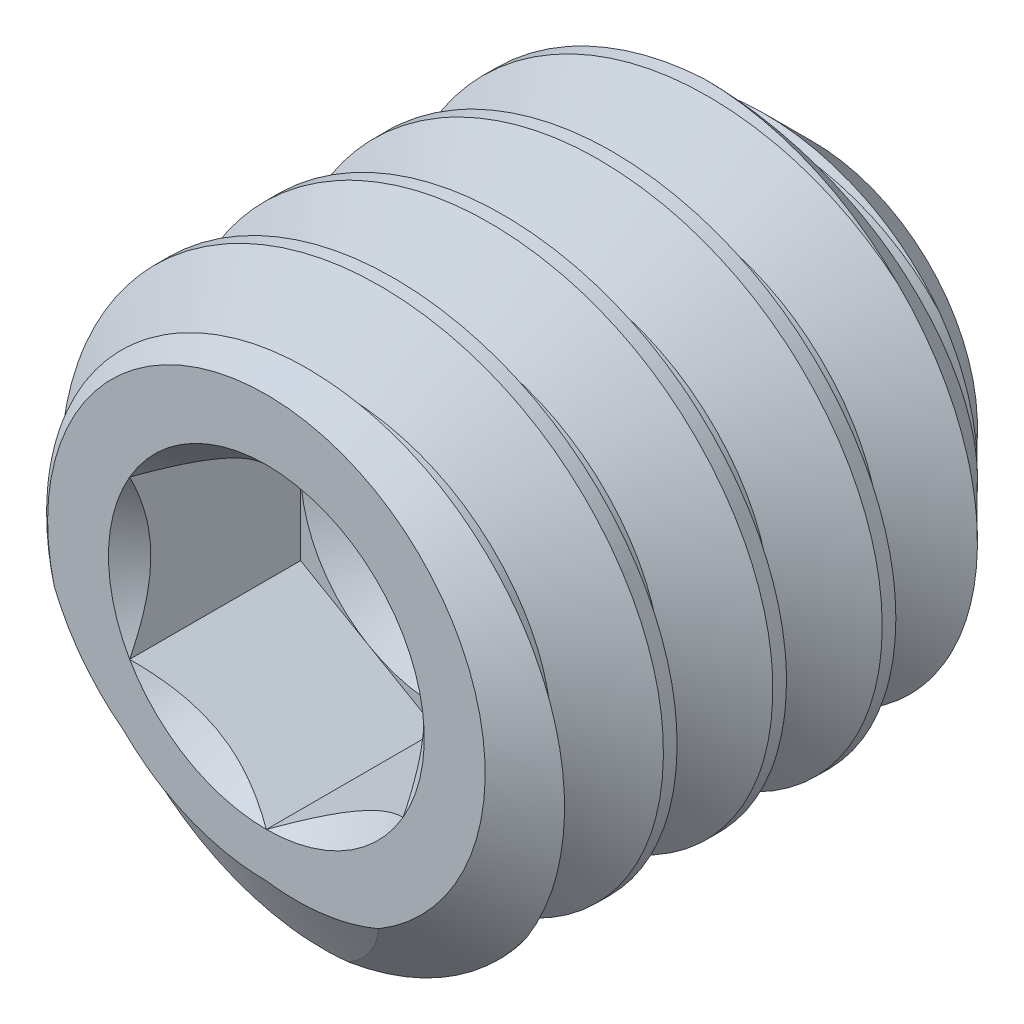
SolidWorks part; units mm, degrees
ref_plane "Front" through (0, 0, 0) normal (0, 0, 1) x (1, 0, 0)
ref_plane "Top" through (0, 0, 0) normal (0, 1, 0) x (1, 0, 0)
ref_plane "Right" through (0, 0, 0) normal (1, 0, 0) x (0, 0, -1)
sketch "Sketch22" plane through (0, 0, 0) normal (1, 0, 0) x (0, 0, -1)
  line L0 (-3.175, 0) -> (-3.175, 2.54)
  line L1 (-3.175, 2.54) -> (-2.7304, 3.175)
  line L2 (-2.7304, 3.175) -> (1.905, 3.175)
  line L3 (1.905, 3.175) -> (3.175, 1.905)
  line L4 (-0.4127, 3.175) -> (-0.4127, -3.175) construction
  line L5 (3.175, 0) -> (-3.175, 0)
  line L7 (3.175, 0) -> (3.175, 1.905)
  line L10 (-3.175, 2.54) -> (-3.175, -2.54) construction
  point P13 (-0.4127, 0)
  dimension "Length" = 6.35
  dimension "D3" = 35
  dimension "D1" = 5.08
  dimension "Dia" = 6.35
  dimension "D2" = 1.27
  dimension "D4" = 45
revolve "Revolve1" add sketch "Sketch22" angle 360 about L5
ref_plane "Plane1" through (0, 0, -3.175) normal (0, 0, 1) x (1, 0, 0)
sketch "Sketch27" plane through (0, 0, -3.175) normal (0, 0, 1) x (1, 0, 0)
  circle A0 centre (0, 0) radius 3.175 construction
  circle A1 centre (0, 0) radius 3.175
curve "Helix/Spiral1" pitch 1.27 height 7.62 radius 3.175 centre (0, 0, -3.175) axis (0, 0, 1) start towards (1, 0, 0)
sketch "Sketch28" plane through (0, 0, 0) normal (1, 0, 0) x (0, 0, -1)
  line L0 (3.175, 3.175) -> (4.2863, 3.175)
  line L1 (4.2863, 3.175) -> (3.81, 2.3501)
  line L2 (3.81, 2.3501) -> (3.6513, 2.3501)
  line L3 (3.6513, 2.3501) -> (3.175, 3.175)
  line L4 (3.4131, 2.7626) -> (4.0481, 2.7626) construction
  line L6 (-2.7304, 3.175) -> (1.905, 3.175) construction
  line L7 (3.175, 2.6543) -> (3.175, -2.6543) construction
  dimension "D1" = 0.1588
  dimension "D3" = 60
  dimension "D2" = 0.635
sweep "Cut-Sweep2" cut profiles "Sketch28" path "Helix/Spiral1" align with end faces yes
sketch "Sketch23" plane through (0, 0, 3.175) normal (0, 0, 1) x (1, 0, 0)
  line L1 (0, 1.8331) -> (-1.5875, 0.9165)
  line L2 (-1.5875, 0.9165) -> (-1.5875, -0.9165)
  line L3 (-1.5875, -0.9165) -> (0, -1.8331)
  line L4 (0, -1.8331) -> (1.5875, -0.9165)
  line L5 (1.5875, -0.9165) -> (1.5875, 0.9165)
  line L6 (1.5875, 0.9165) -> (0, 1.8331)
  circle A0 centre (0, 0) radius 1.5875 construction
  dimension "Hex" = 3.175
extrude "Cut-Extrude10" cut sketch "Sketch23" against normal blind 1.9844
sketch "Sketch24" plane through (0, 0, 3.175) normal (0, 0, 1) x (1, 0, 0)
  circle A0 centre (0, 0) radius 1.8331
extrude "Cut-Extrude11" cut sketch "Sketch24" against normal through all draft 45
sketch "Sketch26" plane through (0, 0, 1.1906) normal (0, 0, 1) x (1, 0, 0)
  circle A0 centre (0, 0) radius 1.5875 construction
  circle A1 centre (0, 0) radius 1.5875
extrude "Cut-Extrude12" cut sketch "Sketch26" against normal through all draft 60
sketch "Sketch30" plane through (0, 0, 0) normal (1, 0, 0) x (0, 0, -1)
  line L0 (-2.7304, 3.175) -> (1.905, 3.175) construction
  line L1 (-3.175, 0) -> (-3.175, 2.54) construction
  line L2 (3.175, 0) -> (3.175, 1.905) construction
  point P0 (-3.175, 3.175)
  point P1 (3.175, 3.175)
  point P2 (3.175, -3.175)
  point P11 (0, -3.175)
  dimension "D1" = 3.175
equation "\"D1@Sketch28\" = \"D4@Helix/Spiral1\" * .125"
equation "\"D3@Helix/Spiral1\" = \"Length@Sketch22\" + \"D4@Helix/Spiral1\""
equation "\"D1@Sketch30\" = \"D4@Helix/Spiral1\" * 2.5"
equation "\"hex Depth@Cut-Extrude10\" = \"Hex@Sketch23\" * .625"
equation "\"D2@Sketch28\" = \"D4@Helix/Spiral1\" * .5"
equation "\"D1@Sketch22\" = \"Dia@Sketch22\" * .8"
equation "\"D2@Sketch22\" = \"D4@Helix/Spiral1\""
